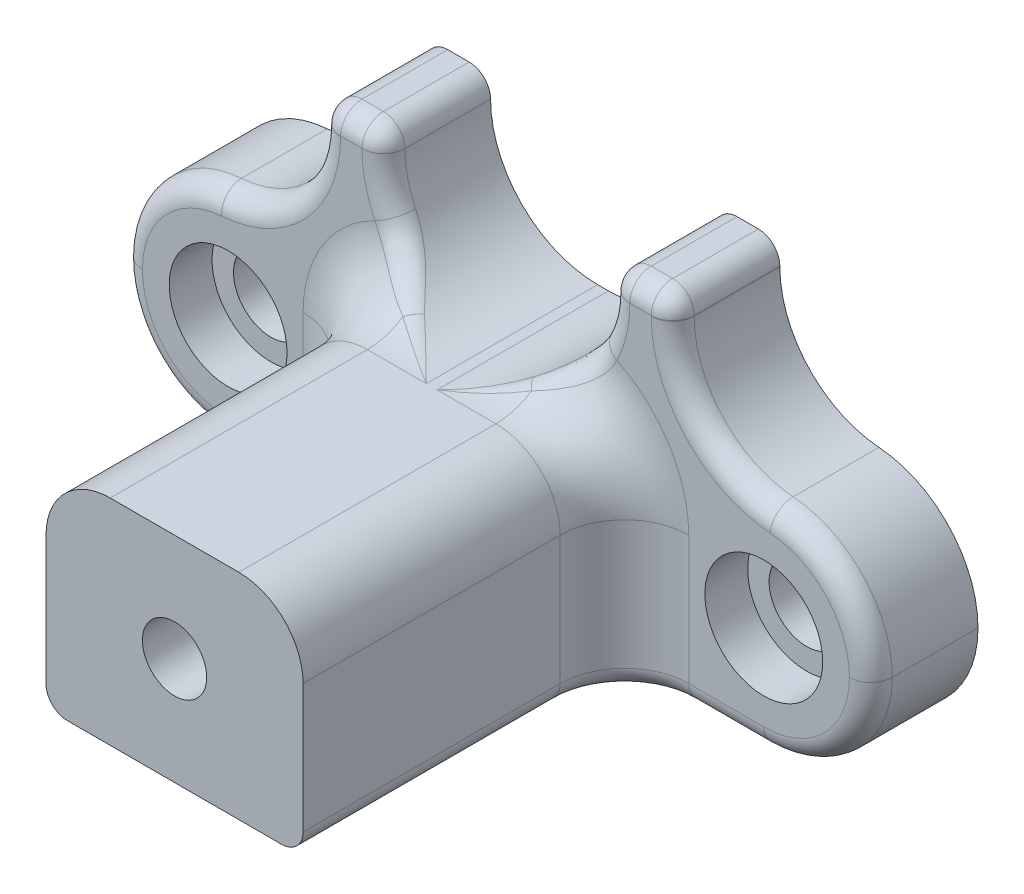
SolidWorks part; units mm, degrees
ref_plane "Front Plane" through (0, 0, 0) normal (0, 0, 1) x (1, 0, 0)
ref_plane "Top Plane" through (0, 0, 0) normal (0, 1, 0) x (1, 0, 0)
ref_plane "Right Plane" through (0, 0, 0) normal (1, 0, 0) x (0, 0, -1)
sketch "Sketch2" plane through (0, 0, 0) normal (0, 0, 1) x (1, 0, 0)
  line L0 (0, 0) -> (35, 0)
  line L1 (35, 0) -> (35, 10)
  line L2 (35, 10) -> (25.75, 10)
  line L3 (0, 10) -> (0, 0)
  line L4 (9.25, 10) -> (9.25, 16)
  line L5 (9.25, 16) -> (12.25, 16)
  line L6 (12.25, 16) -> (12.25, 10)
  line L7 (22.75, 10) -> (22.75, 16)
  line L8 (22.75, 16) -> (25.75, 16)
  line L9 (25.75, 16) -> (25.75, 10)
  line L10 (9.25, 10) -> (0, 10)
  line L11 (22.75, 10) -> (12.25, 10)
  dimension "D1" = 10
  dimension "D2" = 35
  dimension "D3" = 3
  dimension "D4" = 3
  dimension "D5" = 10.5
  dimension "D6" = 6
  dimension "D7" = 9.25
extrude "Boss-Extrude1" add sketch "Sketch2" along normal blind 5
sketch "Sketch3" plane through (0, 0, 5) normal (0, 0, 1) x (1, 0, 0)
  line L0 (11.5, 10) -> (23.5, 10)
  line L1 (9.25, 10) -> (0, 10) construction
  line L2 (35, 10) -> (25.75, 10) construction
  line L3 (23.5, 10) -> (23.5, 0)
  line L4 (0, 0) -> (35, 0) construction
  line L5 (23.5, 0) -> (11.5, 0)
  line L6 (11.5, 0) -> (11.5, 10)
  line L7 (0, 10) -> (0, 0) construction
  dimension "D1" = 12
  dimension "D2" = 11.5
extrude "Boss-Extrude2" add sketch "Sketch3" along normal blind 15
sketch "Sketch4" plane through (0, 0, 5) normal (0, 0, 1) x (1, 0, 0)
  line L0 (9.25, 10) -> (0, 10) construction
  line L1 (0, 10) -> (0, 0) construction
  line L2 (35, 10) -> (25.75, 10) construction
  line L3 (35, 0) -> (35, 10) construction
  circle A0 centre (5, 5) radius 1.75
  circle A1 centre (30, 5) radius 1.75
  dimension "D1" = 3.5
  dimension "D2" = 3.5
  dimension "D3" = 5
  dimension "D4" = 5
  dimension "D5" = 5
  dimension "D6" = 5
extrude "Cut-Extrude1" cut sketch "Sketch4" against normal through all
sketch "Sketch5" plane through (0, 0, 20) normal (0, 0, 1) x (1, 0, 0)
  line L0 (23.5, 10) -> (11.5, 10) construction
  line L1 (11.5, 10) -> (11.5, 0) construction
  circle A0 centre (17.5, 5) radius 1.5
  dimension "D1" = 3
  dimension "D2" = 5
  dimension "D3" = 6
extrude "Cut-Extrude2" cut sketch "Sketch5" against normal blind 7
sketch "Sketch6" plane through (0, 0, 5) normal (0, 0, 1) x (1, 0, 0)
  circle A0 centre (5, 5) radius 2.75
  circle A1 centre (30, 5) radius 2.75
  dimension "D1" = 5.5
  dimension "D2" = 5.5
extrude "Cut-Extrude3" cut sketch "Sketch6" against normal blind 2
fillet "Fillet1" radius 5 4 edges at (35, 10, 2.5) (35, 0, 2.5) (0, 0, 2.5) (0, 10, 2.5)
fillet "Fillet5" radius 5 4 edges at (25.75, 10, 2.5) (9.25, 10, 2.5) (12.25, 10, 2.5) (22.75, 10, 2.5)
fillet "Fillet2" radius 1 4 edges at (9.25, 16, 2.5) (12.25, 16, 2.5) (25.75, 16, 2.5) (22.75, 16, 2.5)
fillet "Fillet3" radius 3 6 edges at (23.5, 10, 12.5) (11.5, 10, 12.5) (23.5, 5, 5) (20.625, 10, 5) (14.375, 10, 5) (11.5, 5, 5)
fillet "Fillet4" radius 1 26 edges at (23.5, 0, 14) (24.3787, 0, 5.8787) (28.25, 0, 5) (33.5355, 1.4645, 5) (33.6657, 8.4004, 5) (24.25, 16, 5) (10.75, 16, 5) (11.5, 0, 14) (10.6213, 0, 5.8787) (6.75, 0, 5) (1.4645, 1.4645, 5) (1.3343, 8.4004, 5) (25.75, 14.9859, 5) (9.25, 14.9859, 5) (23.0429, 15.7071, 5) (25.4571, 15.7071, 5) (11.9571, 15.7071, 5) (9.5429, 15.7071, 5) (18.8356, 10.1193, 7.1625) (21.6651, 11.89, 5.1622) (22.6144, 13.8435, 5) (16.1644, 10.1193, 7.1625) (13.3349, 11.89, 5.1622) (12.3856, 13.8435, 5) (27.0843, 11.5715, 5) (7.9157, 11.5715, 5)
